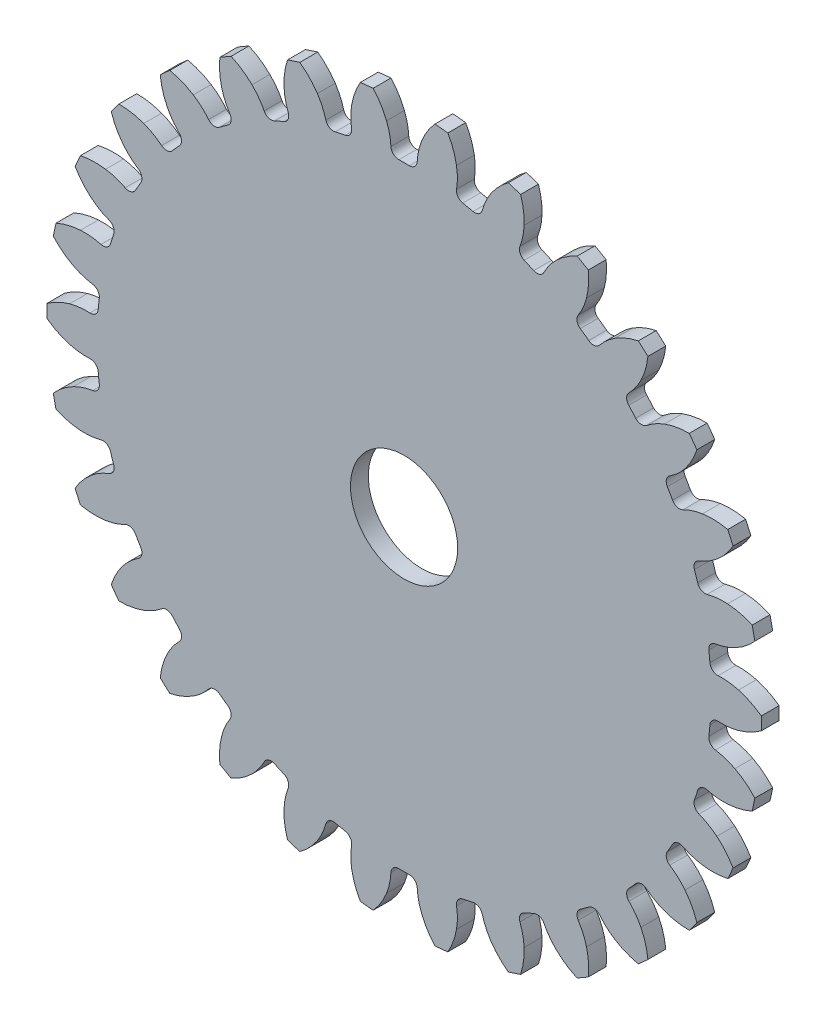
SolidWorks part; units mm, degrees
ref_plane "Front Plane" through (0, 0, 0) normal (0, 0, 1) x (1, 0, 0)
ref_plane "Top Plane" through (0, 0, 0) normal (0, 1, 0) x (1, 0, 0)
ref_plane "Right Plane" through (0, 0, 0) normal (1, 0, 0) x (0, 0, -1)
sketch "Sketch1" plane through (0, 0, 0) normal (0, 0, 1) x (1, 0, 0)
  line L0 (0, 0) -> (47.625, 0) construction
  line L1 (47.625, 0) -> (50.8, 0) construction
  circle A0 centre (0, 0) radius 50.8
  circle A1 centre (0, 0) radius 47.625 construction
  dimension "D2" = 95.25
  dimension "D1" = 3.175
extrude "GEAR_BASE" add sketch "Sketch1" along normal mid plane 2.54
sketch "Sketch2" plane through (0, 0, 1.27) normal (0, 0, 1) x (1, 0, 0)
  line L0 (0, 0) -> (43.6562, 0) construction
  line L1 (43.6562, 0) -> (47.625, 0) construction
  line L2 (0, 0) -> (-50.8, 0) construction
  line L3 (0, 0) -> (-47.5597, -2.494) construction
  line L4 (-47.5597, -2.494) -> (-48.4854, 15.1594) construction
  line L5 (0, 0) -> (-49.6899, -10.5619) construction
  line L6 (-47.5597, -2.494) -> (-43.5589, -2.9143) construction
  line L7 (-47.0389, -7.4487) -> (-43.2129, -6.2057) construction
  line L8 (0, 0) -> (-47.0389, -7.4487) construction
  line L9 (-47.5597, -2.494) -> (-50.7917, -0.9177) construction
  line L10 (-47.0389, -7.4487) -> (-49.8726, -9.6625) construction
  line L11 (-47.0389, -7.4487) -> (-46.5204, -9.8882) construction
  line L12 (-47.0389, -7.4487) -> (-44.274, -24.9088) construction
  line L13 (-47.5597, -2.494) -> (-47.5597, 0) construction
  circle A0 centre (0, 0) radius 47.625 construction
  circle A1 centre (0, 0) radius 43.6562 construction
  circle A2 centre (0, 0) radius 50.8 construction
  arc A3 (-49.8726, -9.6625) -> (-50.7917, -0.9177) centre (0, 0) cw
  arc A4 (-43.4883, -3.8254) -> (-44.6549, -2.8132) centre (-44.5953, -3.9228) ccw
  arc A5 (-44.264, -6.5326) -> (-43.3334, -5.2999) centre (-44.4364, -5.4348) ccw
  arc A6 (-43.3334, -5.2999) -> (-43.4883, -3.8254) centre (0, 0) cw
  arc A7 (-49.8726, -9.6625) -> (-47.0389, -7.4487) centre (-42.4148, -16.2882) cw
  arc A8 (-50.7917, -0.9177) -> (-47.5597, -2.494) centre (-44.8744, 7.1137) ccw
  arc A9 (-47.0389, -7.4487) -> (-44.264, -6.5326) centre (-42.8676, -15.4226) cw
  arc A10 (-47.5597, -2.494) -> (-44.6549, -2.8132) centre (-45.1374, 6.173) ccw
  dimension "D1" = 95.25
  dimension "D11" = 1.1112
  dimension "D12" = 9.9758
  dimension "D2" = 3.9688
  dimension "D3" = 12
  dimension "D5" = 9
  dimension "D7" = 9
  dimension "D8" = 4.9821
  dimension "D9" = 20
  dimension "D10" = 20
  dimension "D6" = 2.494
  dimension "D4" = 2.494
extrude "GEAR_CUT" cut sketch "Sketch2" against normal through all
ref_axis "GEAR_AXIS" through (0, 0, -3.2131) along (0, 0, 1)
pattern_circular "GEAR_TEETH" count 30 over 360 about axis through (0, 0, -3.2131) along (0, 0, 1) of "GEAR_CUT"
sketch "Sketch3" plane through (0, 0, 1.27) normal (0, 0, 1) x (1, 0, 0)
  circle A0 centre (0, 0) radius 4.7625
  dimension "D1" = 9.525
extrude "BORE" cut sketch "Sketch3" against normal through all
sketch "Sketch5" plane through (0, 0, 1.27) normal (0, 0, 1) x (1, 0, 0)
  circle A0 centre (0, 0) radius 7.62
extrude "Cut-Extrude3" cut sketch "Sketch5" against normal through all both and the other way through all
equation "\"N_teeth\"=30"
equation "\"pitch_diameter\"= \"N_teeth\" / \"Pitch\""
equation "\"Pitch\" = 8"
equation "\"addendum\"=1.000/\"Pitch\""
equation "\"face_width\"= \"GMaterial\""
equation "\"deddendum\"=1.250/\"Pitch\""
equation "\"tooth_thickness\"=1.571/\"Pitch\""
equation "\"Pressure_Angle\"=20.000000"
equation "\"base_fillet\"=0.35/\"Pitch\""
equation "\"D1@Sketch1\"=\"addendum\""
equation "\"D2@Sketch1\"=\"pitch_diameter\""
equation "\"D1@GEAR_BASE\" = \"face_width\""
equation "\"D1@Sketch2\"= \"pitch_diameter\""
equation "\"D2@Sketch2\"=\"deddendum\""
equation "\"D4@Sketch2\"=\"tooth_thickness\"/2"
equation "\"D6@Sketch2\"=\"tooth_thickness\"/2"
equation "\"D9@Sketch2\"=\"Pressure_Angle\""
equation "\"D10@Sketch2\"=\"Pressure_Angle\""
equation "\"D11@Sketch2\"=\"base_fillet\""
equation "\"D12@Sketch2\"=2*\"tooth_thickness\""
equation "\"D3@Sketch2\" = 360 / \"N_teeth\""
equation "\"D1@GEAR_TEETH\" = \"N_teeth\""
equation "\"MDF\" = .3in"
equation "\"GMaterial\"= \"Foamcore\""
equation "\"Foamcore\"= .1in"
